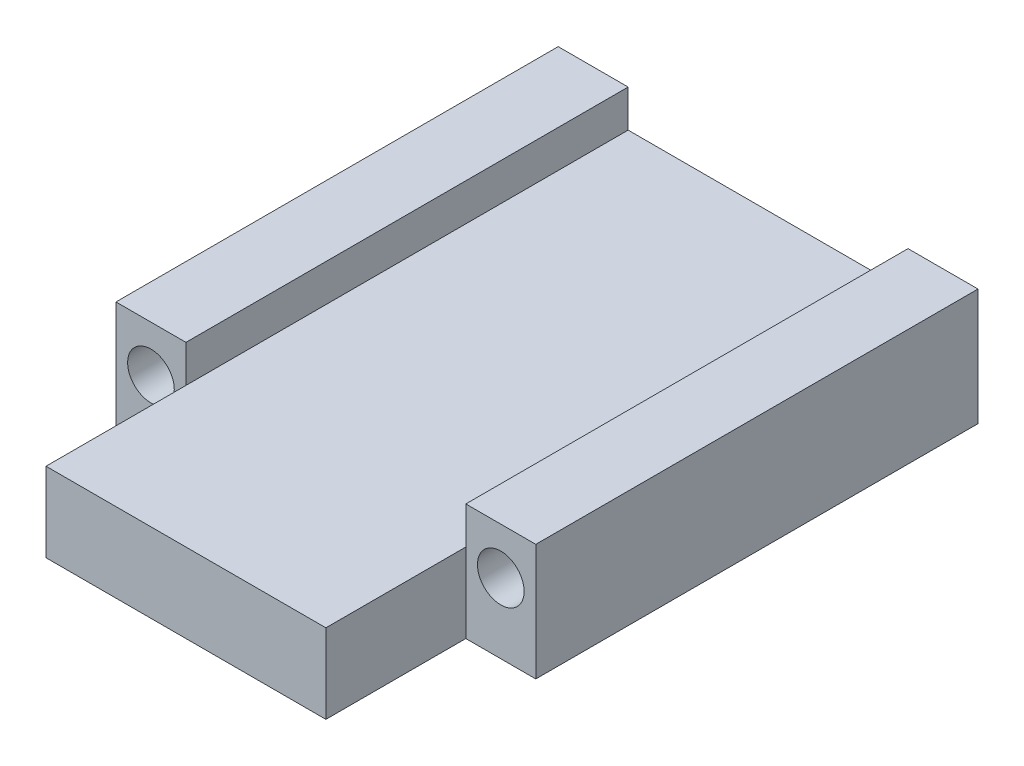
SolidWorks part; units mm, degrees
material "6063-O"
ref_plane "Front" through (0, 0, 0) normal (0, 0, 1) x (1, 0, 0)
ref_plane "Top" through (0, 0, 0) normal (0, 1, 0) x (1, 0, 0)
ref_plane "Right" through (0, 0, 0) normal (1, 0, 0) x (0, 0, -1)
sketch "Sketch1" plane through (0, 0, 0) normal (0, 0, 1) x (1, 0, 0)
  line L1 (14.2875, -3.9687) -> (-14.2875, -3.9688)
  line L2 (14.2875, -3.9687) -> (14.2875, 3.9688)
  line L3 (14.2875, 3.9688) -> (-14.2875, 3.9687)
  line L4 (-14.2875, -3.9688) -> (-14.2875, 3.9687)
  line L5 (14.2875, -3.9687) -> (-14.2875, 3.9687) construction
  line L6 (14.2875, 3.9688) -> (-14.2875, -3.9688) construction
  point P0 (0, 0)
  dimension "D1" = 7.9375
  dimension "D2" = 28.575
extrude "Boss-Extrude1" add sketch "Sketch1" along normal blind 39.624
sketch "Sketch2" plane through (0, 0, 39.624) normal (0, 0, 1) x (1, 0, 0)
  line L0 (9.525, 3.9688) -> (9.525, 1.4288)
  line L1 (14.2875, 3.9688) -> (-14.2875, 3.9688) construction
  line L2 (9.525, 1.4288) -> (-9.525, 1.4288)
  line L3 (-9.525, 1.4288) -> (-9.525, 3.9688)
  line L4 (-9.525, 3.9688) -> (9.525, 3.9688)
  line L5 (0, 0) -> (0, 21.8907) construction
  point P9 (0, 3.9688)
  dimension "D1" = 19.05
  dimension "D2" = 2.54
extrude "Cut-Extrude1" cut sketch "Sketch2" against normal through all
sketch "Sketch3" plane through (0, 0, 0) normal (0, 0, -1) x (-1, 0, 0)
  line L0 (-14.2875, 0.7938) -> (14.2875, 0.7938) construction
  line L1 (-14.2875, -3.9687) -> (-14.2875, 3.9688) construction
  line L2 (14.2875, 3.9687) -> (14.2875, -3.9688) construction
  line L3 (-14.2875, 3.9688) -> (-9.525, 3.9688) construction
  circle A0 centre (-11.9062, 0.7938) radius 1.5875
  circle A1 centre (11.9063, 0.7938) radius 1.5875
  dimension "D3" = 3.175
  dimension "D1" = 3.175
  dimension "D2" = 2.3813
  dimension "D4" = 2.3813
hole_wizard "1/8 (0.125) Clearance Dowel Hole1" positions "Sketch4" profile "Sketch5" hole size "1/8" standard "ANSI Inch" end condition through all
sketch "Sketch4" plane through (0, 0, 0) normal (0, 0, -1) x (-1, 0, 0)
  point P0 (-11.9062, 0.7938)
  point P3 (11.9063, 0.7938)
sketch "Sketch5" plane through (11.9062, 0.7938, 0) normal (1, 0, 0) x (0, 1, 0)
  line L0 (0, 0) -> (0, 39.624)
  line L1 (0, 39.624) -> (1.5875, 39.624)
  line L2 (1.5875, 39.624) -> (1.5875, 0)
  line L5 (1.5875, 0) -> (0, 0)
  line L11 (0, -6.35) -> (0, 107.95) construction
  dimension "Thru Hole Dia." = 3.175
  dimension "Thru Hole Depth" = 39.624
sketch "Sketch6" plane through (0, 0, 39.624) normal (0, 0, 1) x (1, 0, 0)
  line L0 (-14.2875, -3.9688) -> (14.2875, -3.9688) construction
  line L1 (-14.2875, 3.9687) -> (-9.525, 3.9687)
  line L2 (-14.2875, 3.9687) -> (-14.2875, -3.9688)
  line L3 (-14.2875, -3.9688) -> (-9.525, -3.9688)
  line L4 (-9.525, 3.9687) -> (-9.525, -3.9688)
  line L6 (14.2875, 3.9688) -> (9.525, 3.9687)
  line L7 (14.2875, 3.9688) -> (14.2875, -3.9688)
  line L8 (14.2875, -3.9688) -> (9.525, -3.9688)
  line L9 (9.525, 3.9687) -> (9.525, -3.9688)
  dimension "D1" = 4.7625
extrude "Cut-Extrude2" cut sketch "Sketch6" against normal blind 9.525
